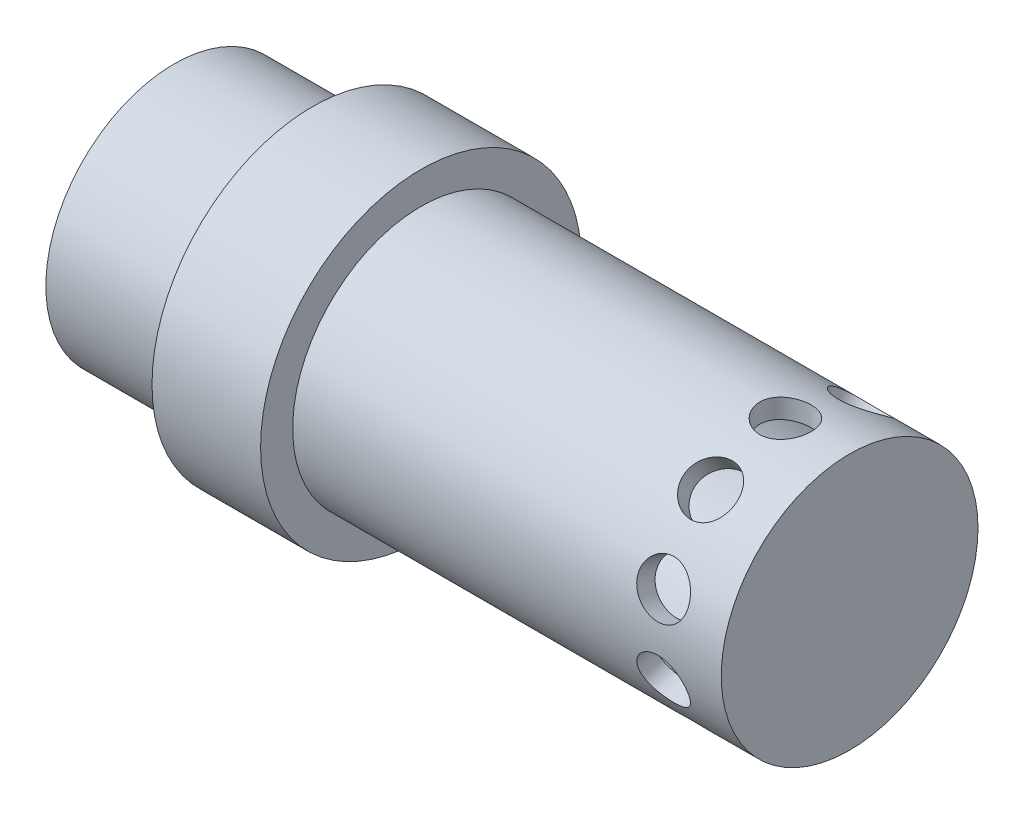
SolidWorks part; units mm, degrees
ref_plane "Front Plane" through (0, 0, 0) normal (0, 0, 1) x (1, 0, 0)
ref_plane "Top Plane" through (0, 0, 0) normal (0, 1, 0) x (1, 0, 0)
ref_plane "Right Plane" through (0, 0, 0) normal (1, 0, 0) x (0, 0, -1)
sketch "CL" plane through (0, 0, 0) normal (0, 0, 1) x (1, 0, 0)
  line L0 (27.575, 0) -> (-130.7221, 0) construction
sketch "Sketch1" plane through (0, 0, 0) normal (0, 0, 1) x (1, 0, 0)
  line L0 (0, 0) -> (0, 20)
  line L2 (0, 20) -> (-66.7844, 20)
  line L4 (-83.703, 20) -> (-105.2449, 20)
  line L5 (-105.2449, 20) -> (-105.2449, 17)
  line L6 (-105.2449, 17) -> (-3, 17)
  line L7 (-3, 17) -> (-3, 0)
  line L8 (-3, 0) -> (0, 0)
  line L9 (-66.7844, 20) -> (-66.7844, 25)
  line L10 (-66.7844, 25) -> (-83.703, 25)
  line L11 (-83.703, 25) -> (-83.703, 20)
  dimension "D1" = 20
  dimension "D2" = 3
  dimension "D3" = 3
  dimension "D4" = 5
revolve "Revolve1" add sketch "Sketch1" angle 360 about L0
sketch "Sketch2" plane through (0, 0, 0) normal (0, 1, 0) x (1, 0, 0)
  line L0 (0, 0) -> (-10, 0) construction
  circle A0 centre (-10, 0) radius 4
  dimension "D1" = 8
  dimension "D2" = 10
extrude "Cut-Extrude1" cut sketch "Sketch2" along normal up to next
pattern_circular "CirPattern1" count 10 over 360 about axis through (27.575, 0, 0) along (-1, 0, 0) of "Cut-Extrude1" reverse direction yes
equation "\"thick\" = 3mm"
equation "\"piston_rad\"= 20mm"
equation "\"D2@Sketch1\"=\"thick\""
equation "\"D1@Sketch1\"=\"piston_rad\""
equation "\"D3@Sketch1\"=\"thick\""
equation "\"spring_lip\"= 5mm"
equation "\"D4@Sketch1\"=\"spring_lip\""
equation "\"injector_dia\" = 8mm"
equation "\"D1@Sketch2\"=\"injector_dia\""
equation "\"injector_hole_offset\"= 10mm"
equation "\"D2@Sketch2\"=\"injector_hole_offset\""
